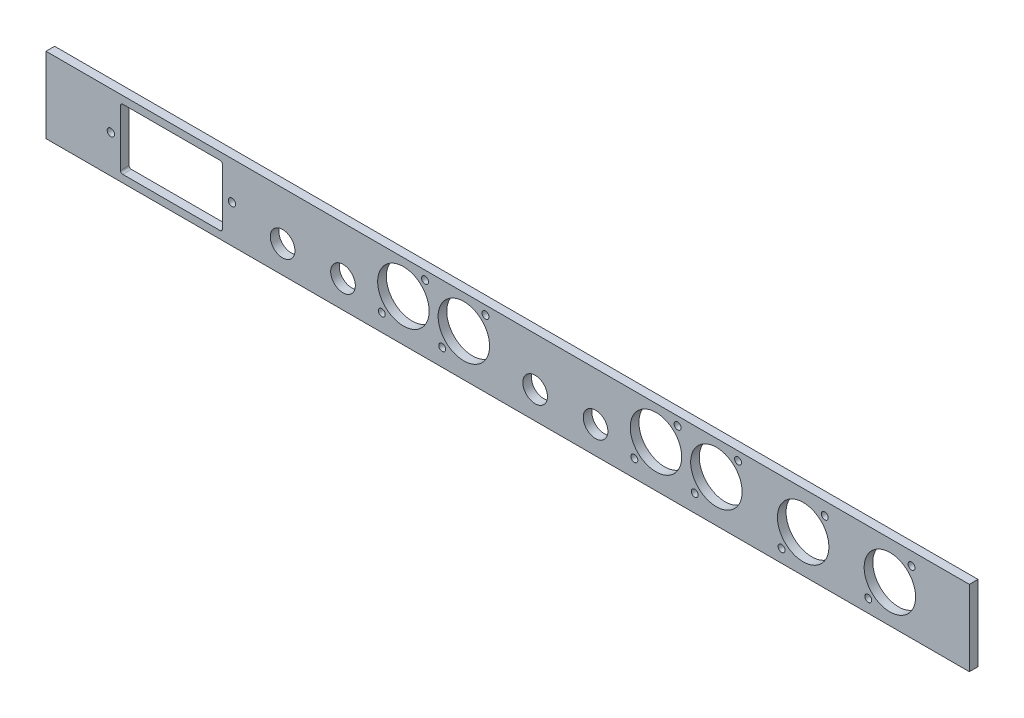
SolidWorks part; units mm, degrees
ref_plane "Front Plane" through (0, 0, 0) normal (0, 0, 1) x (1, 0, 0)
ref_plane "Top Plane" through (0, 0, 0) normal (0, 1, 0) x (1, 0, 0)
ref_plane "Right Plane" through (0, 0, 0) normal (1, 0, 0) x (0, 0, -1)
sketch "Sketch1" plane through (0, 0, 0) normal (0, 0, 1) x (1, 0, 0)
  line L0 (0, 17.5) -> (0, -17.5) construction
  line L1 (-213.5, -17.5) -> (213.5, -17.5)
  line L2 (-213.5, -17.5) -> (-213.5, 17.5)
  line L3 (-213.5, 17.5) -> (213.5, 17.5)
  line L4 (213.5, -17.5) -> (213.5, 17.5)
  line L5 (0, 0) -> (-213.5, 0) construction
  dimension "D1" = 427
  dimension "D2" = 35
extrude "Boss-Extrude1" add sketch "Sketch1" along normal blind 4
sketch "Sketch2" plane through (0, 0, 4) normal (0, 0, 1) x (1, 0, 0)
  line L0 (-116.7918, -2.28) -> (-116.7918, 4.0779) construction
  line L1 (-213.5, 17.5) -> (-213.5, -17.5) construction
  line L2 (-213.5, -17.5) -> (213.5, -17.5) construction
  line L3 (-20.2718, 13.9) -> (-20.2718, -9.9) construction
  line L4 (-48.2118, 13.5) -> (-48.2118, -10.66) construction
  line L6 (-48.2118, 13.5) -> (-38.2118, 13.5) construction
  line L7 (-3.0018, 2.6808) -> (-3.0018, -15.3691) construction
  line L8 (-116.7918, -2.28) -> (-116.7918, 4.0779) construction
  line L9 (-113.1918, 7.9605) -> (-94.9918, 7.9605) construction
  line L11 (0, 17.5) -> (0, -17.5) construction
  line L12 (213.5, 17.5) -> (-213.5, 17.5) construction
  line L15 (-179.05, -14.05) -> (-131.95, 14.05) construction
  line L17 (113.79, 17.5) -> (113.79, -17.2396) construction
  line L18 (-179.05, 14.05) -> (-131.95, -14.05) construction
  line L19 (-213.5, -17.5) -> (213.5, -17.5) construction
  line L20 (-85.2518, 7.9605) -> (-67.0518, 7.9605) construction
  line L21 (87.4177, 2) -> (87.4177, 6.5526) construction
  line L23 (-20.2718, 0) -> (-20.2718, 17.5) construction
  line L25 (-200.5, 17.5) -> (-200.5, -17.5) construction
  line L26 (-213.5, -17.5) -> (213.5, -17.5) construction
  line L27 (-213.5, 17.5) -> (-213.5, -17.5) construction
  line L28 (200.5, -17.5) -> (200.5, 17.5) construction
  line L29 (213.5, -17.5) -> (213.5, 17.5) construction
  line L30 (-213.5, 17.5) -> (213.5, 17.5) construction
  line L34 (-178.05, -14.05) -> (-132.95, -14.05)
  line L35 (-179.05, -13.05) -> (-179.05, 13.05)
  line L36 (-178.05, 14.05) -> (-132.95, 14.05)
  line L37 (-131.95, -13.05) -> (-131.95, 13.05)
  line L38 (0, 17.5) -> (113.79, 17.5) construction
  circle A0 centre (-20.2718, 2) radius 11.9
  circle A1 centre (-30.2718, -9.5) radius 1.6
  circle A2 centre (-10.2718, 13.5) radius 1.6
  circle A3 centre (-58.2118, -9.5) radius 1.6
  circle A4 centre (-48.2118, 2) radius 11.9
  circle A5 centre (-38.2118, 13.5) radius 1.6
  circle A6 centre (126.64, -11.5) radius 1.6
  circle A7 centre (146.64, 11.5) radius 1.6
  circle A8 centre (136.64, 0) radius 11.9
  circle A9 centre (166.76, -11.5) radius 1.6
  circle A10 centre (186.76, 11.5) radius 1.6
  circle A11 centre (176.76, 0) radius 11.9
  circle A12 centre (-76.1518, -4.865) radius 5.7
  circle A13 centre (-104.0918, -4.865) radius 5.7
  circle A14 centre (40.64, -4.865) radius 5.7
  circle A15 centre (86.52, -9.5) radius 1.6
  circle A16 centre (106.52, 13.5) radius 1.6
  circle A17 centre (68.58, 2) radius 11.9
  circle A18 centre (96.52, 2) radius 11.9
  circle A19 centre (12.7, -4.865) radius 5.7
  circle A20 centre (78.58, 13.5) radius 1.6
  circle A21 centre (58.58, -9.5) radius 1.6
  circle A22 centre (-127.5, 0) radius 1.7
  arc A23 (-178.05, -14.05) -> (-179.05, -13.05) centre (-178.05, -13.05) cw
  arc A24 (-131.95, 13.05) -> (-132.95, 14.05) centre (-132.95, 13.05) ccw
  arc A25 (-131.95, -13.05) -> (-132.95, -14.05) centre (-132.95, -13.05) cw
  arc A26 (-179.05, 13.05) -> (-178.05, 14.05) centre (-178.05, 13.05) cw
  circle A27 centre (-183.5, 0) radius 1.7
  point P1 (0, 0)
  point P14 (102.4845, 2)
  point P27 (-60.9232, 2)
  point P32 (-8.3718, 2)
  point P42 (-109.9732, -5.125)
  point P48 (7.2368, 2)
  point P49 (7.2352, -5.0363)
  point P52 (7.2368, 2)
  point P54 (142.6045, 0)
  point P77 (50.6845, 2)
  point P104 (-179.05, 0)
  point P123 (182.7245, 0)
  dimension "D4" = 11.4
  dimension "D2" = 3.2
  dimension "D6" = 11.4
  dimension "D9" = 13
  dimension "D11" = 27.94
  dimension "D22" = 4.45
  dimension "D12" = 4.45
  dimension "D27" = 1
  dimension "D28" = 11.4
  dimension "D29" = 11.4
  dimension "D19" = 47.1
  dimension "D30" = 27.94
  dimension "D32" = 10
  dimension "D33" = 10
  dimension "D34" = 23.8
  dimension "D35" = 10
  dimension "D36" = 20
  dimension "D37" = 23
  dimension "D38" = 23
  dimension "D39" = 23.8
  dimension "D40" = 23.8
  dimension "D41" = 23.8
  dimension "D42" = 3.0018
  dimension "D14" = 20
  dimension "D15" = 23
  dimension "D16" = 10
  dimension "D18" = 12.7
  dimension "D43" = 27.94
  dimension "D45" = 11.5
  dimension "D47" = 11.5
  dimension "D48" = 11.5
  dimension "D49" = 10
  dimension "D50" = 11.5
  dimension "D51" = 9.1
  dimension "D13" = 10
  dimension "D20" = 17.27
  dimension "D23" = 12.635
  dimension "D5" = 23
  dimension "D7" = 27.94
  dimension "D8" = 27.94
  dimension "D10" = 13
  dimension "D17" = 12.7
  dimension "D21" = 19.5
  dimension "D24" = 34.45
  dimension "D25" = 28.1
  dimension "D31" = 27.94
  dimension "D46" = 11.5
  dimension "D52" = 17.27
  dimension "D53" = 9.1
  dimension "D54" = 9.1
  dimension "D55" = 9.1
extrude "Cut-Extrude1" cut sketch "Sketch2" against normal blind 4
